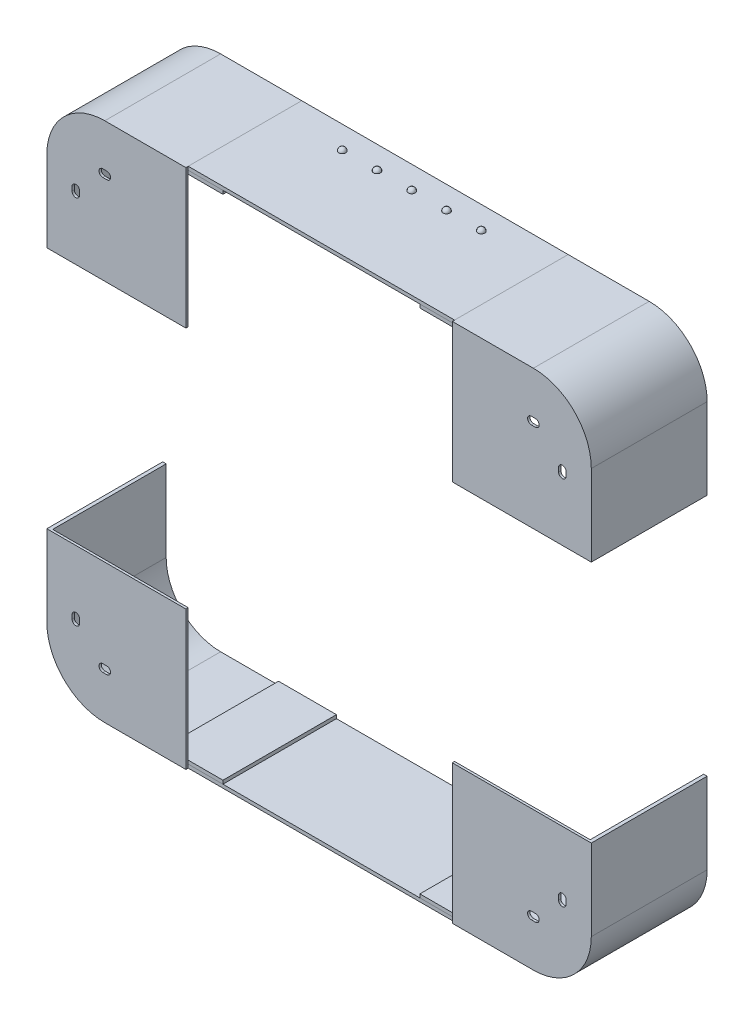
SolidWorks part; units mm, degrees
material "ABS PC"
ref_plane "Front Plane" through (0, 0, 0) normal (0, 0, 1) x (1, 0, 0)
ref_plane "Top Plane" through (0, 0, 0) normal (0, 1, 0) x (1, 0, 0)
ref_plane "Right Plane" through (0, 0, 0) normal (1, 0, 0) x (0, 0, -1)
sketch "Sketch1" plane through (0, 0, 0) normal (0, 0, 1) x (1, 0, 0)
  line L1 (185, 225) -> (-185, 225)
  line L2 (235, 175) -> (235, -175)
  line L3 (185, -225) -> (-185, -225)
  line L4 (-235, 175) -> (-235, -175)
  line L5 (235, 225) -> (-235, -225) construction
  line L6 (235, -225) -> (-235, 225) construction
  arc A0 (-235, -175) -> (-185, -225) centre (-185, -175) ccw
  arc A1 (235, -175) -> (185, -225) centre (185, -175) cw
  arc A2 (185, 225) -> (235, 175) centre (185, 175) cw
  arc A3 (-185, 225) -> (-235, 175) centre (-185, 175) ccw
  point P0 (0, 0)
  dimension "D3" = 50
  dimension "D1" = 450
  dimension "D2" = 470
extrude "Extrude-Thin1" add sketch "Sketch1" along normal blind 100 thin thin type one direction reverse wall 3
sketch "Sketch2" plane through (0, 0, 100) normal (0, 0, 1) x (1, 0, 0)
  line L0 (0, 222) -> (0, -222)
  line L1 (185, 222) -> (-185, 222) construction
  line L2 (-185, -222) -> (185, -222) construction
  line L3 (-232, 175) -> (-232, -175) construction
  line L4 (-185, -222) -> (0, -222)
  line L5 (-232, 175) -> (-232, -175)
  line L6 (0, 222) -> (-185, 222)
  line L8 (0, 141.7622) -> (0, 0) construction
  line L9 (0, 222) -> (185, 222)
  line L10 (232, 175) -> (232, -175)
  line L11 (185, -222) -> (0, -222)
  line L12 (0, 222) -> (0, -222)
  arc A0 (-232, -175) -> (-185, -222) centre (-185, -175) ccw construction
  arc A1 (-185, 222) -> (-232, 175) centre (-185, 175) ccw construction
  arc A2 (-232, -175) -> (-185, -222) centre (-185, -175) ccw
  arc A3 (-185, 222) -> (-232, 175) centre (-185, 175) ccw
  arc A4 (185, 222) -> (232, 175) centre (185, 175) cw
  arc A5 (232, -175) -> (185, -222) centre (185, -175) cw
  line M16 (185, -222) -> (-185, -222)
  arc M17 (-185, -222) -> (-232, -175) centre (-185, -175) cw
  line M18 (-232, -175) -> (-232, 175)
  arc M19 (-232, 175) -> (-185, 222) centre (-185, 175) cw
  line M20 (-185, 222) -> (185, 222)
  arc M21 (185, 222) -> (232, 175) centre (185, 175) cw
  line M22 (232, 175) -> (232, -175)
  arc M23 (232, -175) -> (185, -222) centre (185, -175) cw
extrude "Boss-Extrude1" add sketch "Sketch2" against normal blind 2 contours L0 M20 M19 M18 M17 M16 | L12 M20 M16 M23 M22 M21 region at (115.0199, 0, 100) region at (-115.0199, 0, 100)
sketch "Sketch3" plane through (0, 225, 0) normal (0, 1, 0) x (1, 0, 0)
  line L1 (100, 40) -> (-100, 40)
  line L2 (100, 40) -> (100, -40)
  line L3 (100, -40) -> (-100, -40)
  line L4 (-100, 40) -> (-100, -40)
  line L5 (100, 40) -> (-100, -40) construction
  line L6 (100, -40) -> (-100, 40) construction
  line L7 (185, -100) -> (-185, -100) construction
  point P0 (0, 0)
  dimension "D1" = 80
  dimension "D2" = 200
  dimension "D3" = 100
extrude "Cut-Extrude1" [suppressed] cut sketch "Sketch3" against normal through all and the other way through all
sketch "Sketch6" plane through (0, 0, 100) normal (0, 0, 1) x (1, 0, 0)
  line L0 (-186.75, -181.75) -> (-183.25, -181.75)
  line L1 (-186.75, -188.25) -> (-183.25, -188.25)
  line L2 (0, 0) -> (0, -134.6044) construction
  line L3 (-213.25, -161.75) -> (-213.25, -158.25)
  line L4 (0, 0) -> (55.9692, 0) construction
  line L5 (-206.75, -161.75) -> (-206.75, -158.25)
  line L6 (-235, 175) -> (-235, -175) construction
  line L7 (-185, -225) -> (185, -225) construction
  line L8 (206.75, -161.75) -> (206.75, -158.25)
  line L9 (213.25, -161.75) -> (213.25, -158.25)
  line L10 (186.75, -188.25) -> (183.25, -188.25)
  line L11 (186.75, -181.75) -> (183.25, -181.75)
  line L12 (186.75, 181.75) -> (183.25, 181.75)
  line L13 (186.75, 188.25) -> (183.25, 188.25)
  line L14 (213.25, 161.75) -> (213.25, 158.25)
  line L15 (206.75, 161.75) -> (206.75, 158.25)
  line L16 (-206.75, 161.75) -> (-206.75, 158.25)
  line L17 (-213.25, 161.75) -> (-213.25, 158.25)
  line L18 (-186.75, 188.25) -> (-183.25, 188.25)
  line L19 (-186.75, 181.75) -> (-183.25, 181.75)
  arc A0 (206.75, -158.25) -> (213.25, -158.25) centre (210, -158.25) cw
  arc A3 (-186.75, -181.75) -> (-186.75, -188.25) centre (-186.75, -185) ccw
  arc A4 (183.25, -188.25) -> (183.25, -181.75) centre (183.25, -185) cw
  arc A5 (-213.25, -161.75) -> (-206.75, -161.75) centre (-210, -161.75) ccw
  arc A6 (-183.25, -188.25) -> (-183.25, -181.75) centre (-183.25, -185) ccw
  arc A7 (-206.75, -158.25) -> (-213.25, -158.25) centre (-210, -158.25) ccw
  arc A8 (213.25, -161.75) -> (206.75, -161.75) centre (210, -161.75) cw
  arc A9 (186.75, -181.75) -> (186.75, -188.25) centre (186.75, -185) cw
  arc A10 (186.75, 181.75) -> (186.75, 188.25) centre (186.75, 185) ccw
  arc A11 (213.25, 161.75) -> (206.75, 161.75) centre (210, 161.75) ccw
  arc A12 (-206.75, 158.25) -> (-213.25, 158.25) centre (-210, 158.25) cw
  arc A13 (-183.25, 188.25) -> (-183.25, 181.75) centre (-183.25, 185) cw
  arc A14 (-213.25, 161.75) -> (-206.75, 161.75) centre (-210, 161.75) cw
  arc A15 (183.25, 188.25) -> (183.25, 181.75) centre (183.25, 185) ccw
  arc A16 (-186.75, 181.75) -> (-186.75, 188.25) centre (-186.75, 185) cw
  arc A17 (206.75, 158.25) -> (213.25, 158.25) centre (210, 158.25) ccw
  dimension "D1" = 3.25
  dimension "D2" = 25
  dimension "D3" = 63.25
  dimension "D4" = 3.5
  dimension "D5" = 40
  dimension "D6" = 48.25
  dimension "D7" = 3.5
extrude "Cut-Extrude3" cut sketch "Sketch6" against normal blind 10
ref_plane "Plane1" through (232, -175, 0) normal (0, 1, 0) x (1, 0, 0)
sketch "Sketch7" plane through (0, -225, 0) normal (0, -1, 0) x (1, 0, 0)
  line L0 (-185, 0) -> (185, 0) construction
  line L1 (-115, 0) -> (115, 0)
  line L2 (-115, 0) -> (-115, 100)
  line L3 (-115, 100) -> (115, 100)
  line L4 (115, 0) -> (115, 100)
  line L5 (-235, 100) -> (-235, 0) construction
  line L6 (235, 100) -> (235, 0) construction
  dimension "D1" = 120
  dimension "D2" = 100
  dimension "D3" = 120
extrude "Cut-Extrude4" cut sketch "Sketch7" against normal through all both and the other way through all
sketch "Sketch5" plane through (235, -10, 0) normal (-1, 0, 0) x (0, -1, 0)
  line L0 (215, 100) -> (215, 0) construction
  line L1 (95, -396.7147) -> (-115, -396.7147)
  line L2 (95, -396.7147) -> (95, 157.674)
  line L3 (95, 157.674) -> (-115, 157.674)
  line L4 (-115, -396.7147) -> (-115, 157.674)
  line L5 (95, -396.7147) -> (-115, 157.674) construction
  line L6 (95, 157.674) -> (-115, -396.7147) construction
  line L7 (-235, 100) -> (-235, 0) construction
  point P0 (-10, 7.5083)
  point P10 (0, 0)
  point P11 (-106.4812, 157.674)
  point P12 (-125, -51.8754)
  point P13 (-10, 7.5083)
  point P14 (-125, -396.7147)
  dimension "D1" = 120
  dimension "D2" = 120
  dimension "D3" = 120
extrude "Cut-Extrude5" cut sketch "Sketch5" along normal through all both
sketch "Sketch9" plane through (0, 222, 0) normal (0, -1, 0) x (1, 0, 0)
  line L0 (-115, 0) -> (-185, 0) construction
  line L1 (-135, 0) -> (-85, 0)
  line L2 (-135, 0) -> (-135, 98)
  line L3 (-135, 98) -> (-85, 98)
  line L4 (135, 0) -> (135, 98)
  line L5 (115, 0) -> (115, 98) construction
  line L6 (-115, 98) -> (-115, 0) construction
  line L7 (-185, 98) -> (-115, 98) construction
  line L8 (85, 98) -> (135, 98)
  line L10 (-85, 98) -> (-85, 0)
  line L12 (85, 98) -> (85, 0)
  line L13 (85, 0) -> (135, 0)
  dimension "D1" = 20
  dimension "D2" = 20
  dimension "D3" = 50
  dimension "D4" = 50
extrude "Boss-Extrude2" add sketch "Sketch9" along normal blind 3 separate body
sketch "Sketch10" plane through (0, 222, 0) normal (0, 1, 0) x (1, 0, 0)
  line L1 (-115, 0) -> (115, 0)
  line L2 (-115, 0) -> (-115, -98)
  line L3 (-115, -98) -> (115, -98)
  line L4 (115, 0) -> (115, -98)
extrude "Boss-Extrude3" add sketch "Sketch10" along normal blind 3 separate body
mirror "Mirror2" about plane through (0, 0, 0) normal (0, 1, 0) of bodies 131 132 135
sketch "Sketch11" plane through (0, -225, 0) normal (0, -1, 0) x (1, 0, 0)
  line L0 (115, 0) -> (-115, 0) construction
  circle A0 centre (-60, 20) radius 3
  circle A1 centre (60, 20) radius 3
  circle A2 centre (0, 20) radius 3
  circle A3 centre (-30, 20) radius 3
  circle A4 centre (30, 20) radius 3
  point P10 (0, 0)
  dimension "D1" = 20
  dimension "D2" = 6
  dimension "D3" = 60
  dimension "D4" = 30
  dimension "D5" = 30
  dimension "D6" = 30
  dimension "D7" = 20
extrude "Boss-Extrude4" add sketch "Sketch11" along normal blind 6
fillet "Fillet1" radius 3 5 edges at (63, -231, 20) (33, -231, 20) (3, -231, 20) (-27, -231, 20) (-57, -231, 20)
sketch "Sketch12" plane through (0, 222, 0) normal (0, -1, 0) x (1, 0, 0)
  circle A0 centre (-60, 20) radius 3 construction
  circle A1 centre (60, 20) radius 3 construction
  circle A2 centre (30, 20) radius 3 construction
  circle A3 centre (0, 20) radius 3 construction
  circle A4 centre (-30, 20) radius 3 construction
  circle A5 centre (-60, 20) radius 3
  circle A6 centre (60, 20) radius 3
  circle A7 centre (30, 20) radius 3
  circle A8 centre (0, 20) radius 3
  circle A9 centre (-30, 20) radius 3
extrude "Boss-Extrude5" add sketch "Sketch12" against normal blind 6
fillet "Fillet2" radius 3 5 edges at (63, 228, 20) (33, 228, 20) (3, 228, 20) (-27, 228, 20) (-57, 228, 20)
